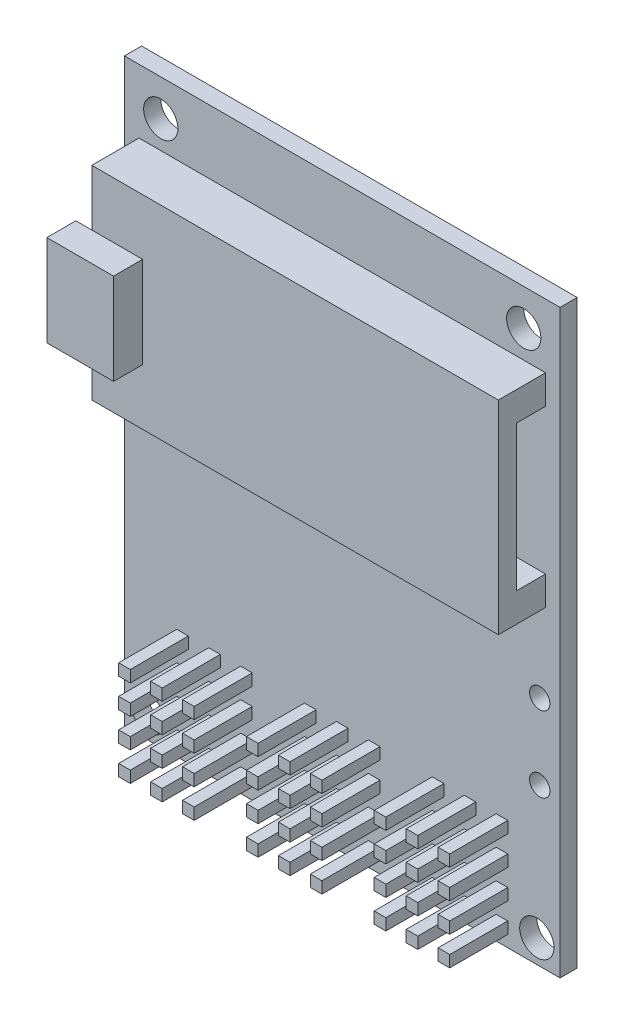
SolidWorks part; units mm, degrees
ref_plane "Front Plane" through (0, 0, 0) normal (0, 0, 1) x (1, 0, 0)
ref_plane "Top Plane" through (0, 0, 0) normal (0, 1, 0) x (1, 0, 0)
ref_plane "Right Plane" through (0, 0, 0) normal (1, 0, 0) x (0, 0, -1)
sketch "Sketch1" plane through (0, 0, 0) normal (0, 0, 1) x (1, 0, 0)
  line L0 (0, 25.4) -> (0, -25.4) construction
  line L1 (19.05, -25.4) -> (-19.05, -25.4)
  line L2 (19.05, -25.4) -> (19.05, 25.4)
  line L3 (19.05, 25.4) -> (-19.05, 25.4)
  line L4 (-19.05, -25.4) -> (-19.05, 25.4)
  line L5 (19.05, -25.4) -> (-19.05, 25.4) construction
  line L6 (19.05, 25.4) -> (-19.05, -25.4) construction
  circle A0 centre (-17.018, -23.368) radius 1.5
  circle A1 centre (-15.875, 22.225) radius 1.5
  circle A2 centre (17.018, -23.368) radius 1.5
  circle A3 centre (15.875, 22.225) radius 1.5
  point P0 (0, 0)
  dimension "D5" = 3
  dimension "D1" = 38.1
  dimension "D2" = 50.8
  dimension "D3" = 2.032
  dimension "D4" = 2.032
  dimension "D6" = 3.175
  dimension "D7" = 3.175
extrude "Boss-Extrude1" add sketch "Sketch1" along normal blind 1.5
sketch "Sketch2" plane through (0, 0, 1.5) normal (0, 0, 1) x (1, 0, 0)
  line L0 (19.05, -25.4) -> (19.05, 25.4) construction
  line L1 (-19.05, -25.4) -> (19.05, -25.4) construction
  circle A0 centre (17.272, -11.684) radius 0.889
  circle A1 centre (17.272, -5.08) radius 0.889
  dimension "D3" = 1.778
  dimension "D1" = 1.778
  dimension "D2" = 13.716
  dimension "D4" = 6.604
  dimension "D5" = 1.778
extrude "Cut-Extrude1" cut sketch "Sketch2" against normal through all
sketch "Sketch3" plane through (0, 0, 1.5) normal (0, 0, 1) x (1, 0, 0)
  line L0 (-19.05, -23.876) -> (-13.97, -23.876) construction
  line L1 (-19.05, 25.4) -> (-19.05, -25.4) construction
  line L2 (-19.05, -25.4) -> (19.05, -25.4) construction
  line L3 (-13.462, -24.384) -> (-14.478, -24.384)
  line L4 (-13.462, -24.384) -> (-13.462, -23.368)
  line L5 (-13.462, -23.368) -> (-14.478, -23.368)
  line L6 (-14.478, -24.384) -> (-14.478, -23.368)
  line L7 (-13.462, -24.384) -> (-14.478, -23.368) construction
  line L8 (-13.462, -23.368) -> (-14.478, -24.384) construction
  line L9 (-13.462, -20.828) -> (-14.478, -20.828)
  line L10 (-13.462, -21.844) -> (-13.462, -20.828)
  line L11 (-13.462, -21.844) -> (-14.478, -21.844)
  line L12 (-14.478, -21.844) -> (-14.478, -20.828)
  line L13 (-13.462, -18.288) -> (-14.478, -18.288)
  line L14 (-13.462, -19.304) -> (-13.462, -18.288)
  line L15 (-13.462, -19.304) -> (-14.478, -19.304)
  line L16 (-14.478, -19.304) -> (-14.478, -18.288)
  line L17 (-13.462, -15.748) -> (-14.478, -15.748)
  line L18 (-13.462, -16.764) -> (-13.462, -15.748)
  line L19 (-13.462, -16.764) -> (-14.478, -16.764)
  line L20 (-14.478, -16.764) -> (-14.478, -15.748)
  line L21 (-10.668, -23.368) -> (-11.684, -23.368)
  line L22 (-10.668, -24.384) -> (-10.668, -23.368)
  line L23 (-10.668, -24.384) -> (-11.684, -24.384)
  line L24 (-11.684, -24.384) -> (-11.684, -23.368)
  line L25 (-10.668, -20.828) -> (-11.684, -20.828)
  line L26 (-10.668, -21.844) -> (-10.668, -20.828)
  line L27 (-10.668, -21.844) -> (-11.684, -21.844)
  line L28 (-11.684, -21.844) -> (-11.684, -20.828)
  line L29 (-10.668, -18.288) -> (-11.684, -18.288)
  line L30 (-10.668, -19.304) -> (-10.668, -18.288)
  line L31 (-10.668, -19.304) -> (-11.684, -19.304)
  line L32 (-11.684, -19.304) -> (-11.684, -18.288)
  line L33 (-10.668, -15.748) -> (-11.684, -15.748)
  line L34 (-10.668, -16.764) -> (-10.668, -15.748)
  line L35 (-10.668, -16.764) -> (-11.684, -16.764)
  line L36 (-11.684, -16.764) -> (-11.684, -15.748)
  line L37 (-7.874, -23.368) -> (-8.89, -23.368)
  line L38 (-7.874, -24.384) -> (-7.874, -23.368)
  line L39 (-7.874, -24.384) -> (-8.89, -24.384)
  line L40 (-8.89, -24.384) -> (-8.89, -23.368)
  line L41 (-7.874, -20.828) -> (-8.89, -20.828)
  line L42 (-7.874, -21.844) -> (-7.874, -20.828)
  line L43 (-7.874, -21.844) -> (-8.89, -21.844)
  line L44 (-8.89, -21.844) -> (-8.89, -20.828)
  line L45 (-7.874, -18.288) -> (-8.89, -18.288)
  line L46 (-7.874, -19.304) -> (-7.874, -18.288)
  line L47 (-7.874, -19.304) -> (-8.89, -19.304)
  line L48 (-8.89, -19.304) -> (-8.89, -18.288)
  line L49 (-7.874, -15.748) -> (-8.89, -15.748)
  line L50 (-7.874, -16.764) -> (-7.874, -15.748)
  line L51 (-7.874, -16.764) -> (-8.89, -16.764)
  line L52 (-8.89, -16.764) -> (-8.89, -15.748)
  line L53 (-2.286, -23.368) -> (-3.302, -23.368)
  line L54 (-2.286, -24.384) -> (-2.286, -23.368)
  line L55 (-2.286, -24.384) -> (-3.302, -24.384)
  line L56 (-3.302, -24.384) -> (-3.302, -23.368)
  line L57 (-2.286, -20.828) -> (-3.302, -20.828)
  line L58 (-2.286, -21.844) -> (-2.286, -20.828)
  line L59 (-2.286, -21.844) -> (-3.302, -21.844)
  line L60 (-3.302, -21.844) -> (-3.302, -20.828)
  line L61 (-2.286, -18.288) -> (-3.302, -18.288)
  line L62 (-2.286, -19.304) -> (-2.286, -18.288)
  line L63 (-2.286, -19.304) -> (-3.302, -19.304)
  line L64 (-3.302, -19.304) -> (-3.302, -18.288)
  line L65 (-2.286, -15.748) -> (-3.302, -15.748)
  line L66 (-2.286, -16.764) -> (-2.286, -15.748)
  line L67 (-2.286, -16.764) -> (-3.302, -16.764)
  line L68 (-3.302, -16.764) -> (-3.302, -15.748)
  line L69 (0.508, -23.368) -> (-0.508, -23.368)
  line L70 (0.508, -24.384) -> (0.508, -23.368)
  line L71 (0.508, -24.384) -> (-0.508, -24.384)
  line L72 (-0.508, -24.384) -> (-0.508, -23.368)
  line L73 (0.508, -20.828) -> (-0.508, -20.828)
  line L74 (0.508, -21.844) -> (0.508, -20.828)
  line L75 (0.508, -21.844) -> (-0.508, -21.844)
  line L76 (-0.508, -21.844) -> (-0.508, -20.828)
  line L77 (0.508, -18.288) -> (-0.508, -18.288)
  line L78 (0.508, -19.304) -> (0.508, -18.288)
  line L79 (0.508, -19.304) -> (-0.508, -19.304)
  line L80 (-0.508, -19.304) -> (-0.508, -18.288)
  line L81 (0.508, -15.748) -> (-0.508, -15.748)
  line L82 (0.508, -16.764) -> (0.508, -15.748)
  line L83 (0.508, -16.764) -> (-0.508, -16.764)
  line L84 (-0.508, -16.764) -> (-0.508, -15.748)
  line L85 (3.302, -23.368) -> (2.286, -23.368)
  line L86 (3.302, -24.384) -> (3.302, -23.368)
  line L87 (3.302, -24.384) -> (2.286, -24.384)
  line L88 (2.286, -24.384) -> (2.286, -23.368)
  line L89 (3.302, -20.828) -> (2.286, -20.828)
  line L90 (3.302, -21.844) -> (3.302, -20.828)
  line L91 (3.302, -21.844) -> (2.286, -21.844)
  line L92 (2.286, -21.844) -> (2.286, -20.828)
  line L93 (3.302, -18.288) -> (2.286, -18.288)
  line L94 (3.302, -19.304) -> (3.302, -18.288)
  line L95 (3.302, -19.304) -> (2.286, -19.304)
  line L96 (2.286, -19.304) -> (2.286, -18.288)
  line L97 (3.302, -15.748) -> (2.286, -15.748)
  line L98 (3.302, -16.764) -> (3.302, -15.748)
  line L99 (3.302, -16.764) -> (2.286, -16.764)
  line L100 (2.286, -16.764) -> (2.286, -15.748)
  line L101 (8.89, -23.368) -> (7.874, -23.368)
  line L102 (8.89, -24.384) -> (8.89, -23.368)
  line L103 (8.89, -24.384) -> (7.874, -24.384)
  line L104 (7.874, -24.384) -> (7.874, -23.368)
  line L105 (8.89, -20.828) -> (7.874, -20.828)
  line L106 (8.89, -21.844) -> (8.89, -20.828)
  line L107 (8.89, -21.844) -> (7.874, -21.844)
  line L108 (7.874, -21.844) -> (7.874, -20.828)
  line L109 (8.89, -18.288) -> (7.874, -18.288)
  line L110 (8.89, -19.304) -> (8.89, -18.288)
  line L111 (8.89, -19.304) -> (7.874, -19.304)
  line L112 (7.874, -19.304) -> (7.874, -18.288)
  line L113 (8.89, -15.748) -> (7.874, -15.748)
  line L114 (8.89, -16.764) -> (8.89, -15.748)
  line L115 (8.89, -16.764) -> (7.874, -16.764)
  line L116 (7.874, -16.764) -> (7.874, -15.748)
  line L117 (11.684, -23.368) -> (10.668, -23.368)
  line L118 (11.684, -24.384) -> (11.684, -23.368)
  line L119 (11.684, -24.384) -> (10.668, -24.384)
  line L120 (10.668, -24.384) -> (10.668, -23.368)
  line L121 (11.684, -20.828) -> (10.668, -20.828)
  line L122 (11.684, -21.844) -> (11.684, -20.828)
  line L123 (11.684, -21.844) -> (10.668, -21.844)
  line L124 (10.668, -21.844) -> (10.668, -20.828)
  line L125 (11.684, -18.288) -> (10.668, -18.288)
  line L126 (11.684, -19.304) -> (11.684, -18.288)
  line L127 (11.684, -19.304) -> (10.668, -19.304)
  line L128 (10.668, -19.304) -> (10.668, -18.288)
  line L129 (11.684, -15.748) -> (10.668, -15.748)
  line L130 (11.684, -16.764) -> (11.684, -15.748)
  line L131 (11.684, -16.764) -> (10.668, -16.764)
  line L132 (10.668, -16.764) -> (10.668, -15.748)
  line L133 (14.478, -23.368) -> (13.462, -23.368)
  line L134 (14.478, -24.384) -> (14.478, -23.368)
  line L135 (14.478, -24.384) -> (13.462, -24.384)
  line L136 (13.462, -24.384) -> (13.462, -23.368)
  line L137 (14.478, -20.828) -> (13.462, -20.828)
  line L138 (14.478, -21.844) -> (14.478, -20.828)
  line L139 (14.478, -21.844) -> (13.462, -21.844)
  line L140 (13.462, -21.844) -> (13.462, -20.828)
  line L141 (14.478, -18.288) -> (13.462, -18.288)
  line L142 (14.478, -19.304) -> (14.478, -18.288)
  line L143 (14.478, -19.304) -> (13.462, -19.304)
  line L144 (13.462, -19.304) -> (13.462, -18.288)
  line L145 (14.478, -15.748) -> (13.462, -15.748)
  line L146 (14.478, -16.764) -> (14.478, -15.748)
  line L147 (14.478, -16.764) -> (13.462, -16.764)
  line L148 (13.462, -16.764) -> (13.462, -15.748)
  dimension "D1" = 5.08
  dimension "D2" = 1.016
  dimension "D3" = 1.016
  dimension "D4" = 1.524
  dimension "D5" = 4
  dimension "D6" = 3
  dimension "D7" = 3
extrude "Boss-Extrude2" add sketch "Sketch3" along normal blind 5.08
sketch "Sketch5" plane through (0, 0, 1.5) normal (0, 0, 1) x (1, 0, 0)
  line L0 (0, 20.6375) -> (0, -4.7625) construction
  line L1 (17.78, 19.812) -> (17.78, 17.272)
  line L2 (-19.05, -25.4) -> (19.05, -25.4) construction
  line L3 (-17.78, 19.812) -> (17.78, 19.812)
  line L4 (-17.78, 19.812) -> (-17.78, 2.032)
  line L5 (-17.78, 2.032) -> (17.78, 2.032)
  line L6 (17.78, 17.272) -> (15.24, 17.272)
  line L7 (-17.78, 19.812) -> (17.78, 2.032) construction
  line L8 (-17.78, 2.032) -> (17.78, 19.812) construction
  line L9 (-15.24, 4.572) -> (15.24, 4.572)
  line L10 (17.78, 2.032) -> (17.78, 4.572)
  line L11 (-15.24, 17.272) -> (15.24, 17.272)
  line L12 (-15.24, 17.272) -> (-15.24, 4.572)
  line L13 (15.24, 17.272) -> (15.24, 4.572) construction
  line L14 (17.78, 19.812) -> (17.78, 2.032) construction
  line L15 (-19.05, 25.4) -> (-19.05, -25.4) construction
  line L16 (17.78, 4.572) -> (15.24, 4.572)
  point P1 (0, 10.922)
  dimension "D1" = 36.322
  dimension "D2" = 17.78
  dimension "D3" = 35.56
  dimension "D5" = 19.05
  dimension "D4" = 2.54
extrude "Boss-Extrude3" add sketch "Sketch5" along normal blind 2.54
sketch "Sketch6" plane through (0, 0, 4.04) normal (0, 0, 1) x (1, 0, 0)
  line L1 (-17.78, 19.812) -> (17.78, 19.812)
  line L2 (-17.78, 19.812) -> (-17.78, 2.032)
  line L3 (-17.78, 2.032) -> (17.78, 2.032)
  line L4 (17.78, 19.812) -> (17.78, 2.032)
extrude "Boss-Extrude4" add sketch "Sketch6" along normal blind 1.5875
sketch "Sketch7" plane through (0, 0, 5.6275) normal (0, 0, 1) x (1, 0, 0)
  line L0 (17.78, 10.922) -> (-17.78, 10.922) construction
  line L1 (17.78, 2.032) -> (17.78, 19.812) construction
  line L2 (-17.78, 19.812) -> (-17.78, 2.032) construction
  line L9 (0, 19.812) -> (0, 2.032) construction
  line L10 (17.78, 19.812) -> (-17.78, 19.812) construction
  line L11 (-17.78, 2.032) -> (17.78, 2.032) construction
  line L12 (-17.78, 14.9098) -> (-19.177, 14.9098)
  line L13 (-19.177, 14.9098) -> (-19.177, 6.9342)
  line L14 (-17.78, 6.9342) -> (-19.177, 6.9342)
  line L15 (-17.78, 6.9342) -> (-13.335, 6.9342)
  line L16 (-13.335, 14.9098) -> (-13.335, 6.9342)
  line L17 (-17.78, 14.9098) -> (-13.335, 14.9098)
  point P13 (19.177, 10.922)
  point P14 (13.335, 10.922)
extrude "Boss-Extrude5" add sketch "Sketch7" along normal blind 2.54
